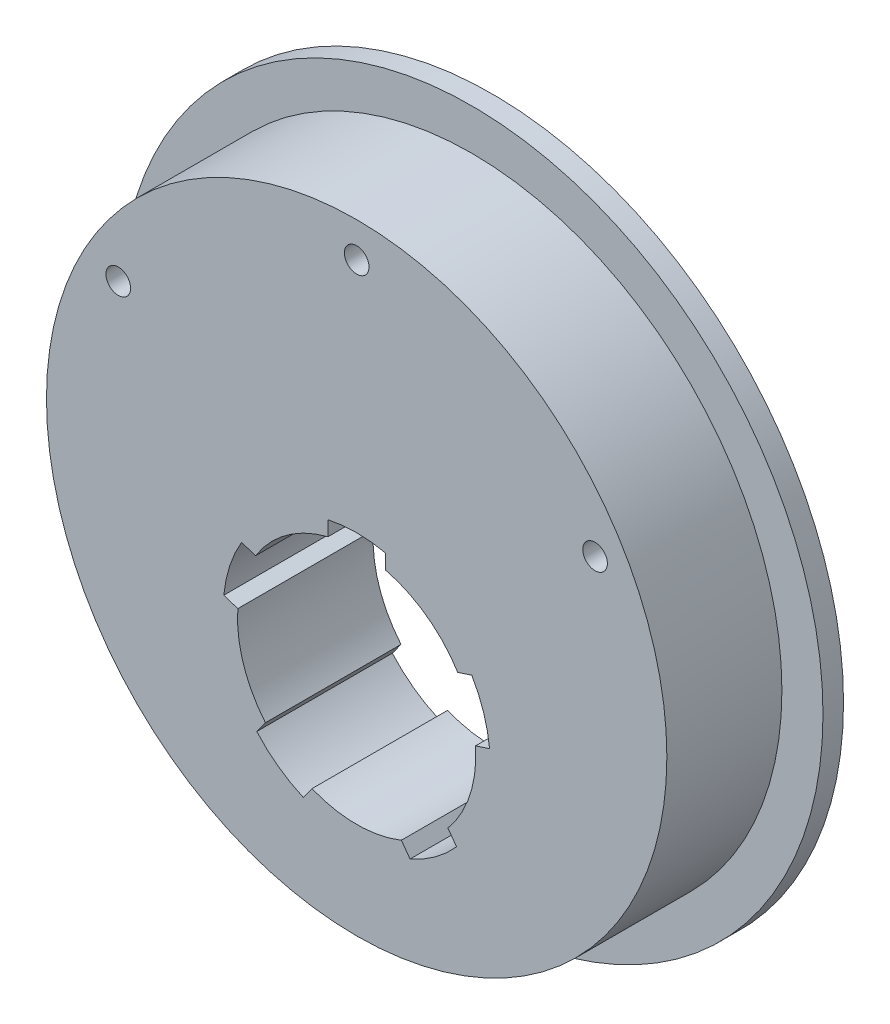
SolidWorks part; units mm, degrees
ref_plane "Front Plane" through (0, 0, 0) normal (0, 0, 1) x (1, 0, 0)
ref_plane "Top Plane" through (0, 0, 0) normal (0, 1, 0) x (1, 0, 0)
ref_plane "Right Plane" through (0, 0, 0) normal (1, 0, 0) x (0, 0, -1)
sketch "Sketch2" plane through (0, 0, 0) normal (0, 0, 1) x (1, 0, 0)
  circle A0 centre (0, 0) radius 85.5
  dimension "D1" = 171
extrude "Boss-Extrude1" add sketch "Sketch2" along normal blind 5
sketch "Sketch4" plane through (0, 0, 5) normal (0, 0, 1) x (1, 0, 0)
  circle A0 centre (0, 0) radius 75.5
  dimension "D1" = 151
extrude "Boss-Extrude2" add sketch "Sketch4" along normal blind 28
sketch "Sketch5" plane through (0, 0, 33) normal (0, 0, 1) x (1, 0, 0)
  circle A4 centre (0, -23) radius 29
  point P3 (0, 0)
  point P17 (-3.5, -55.5)
  dimension "D1" = 58
  dimension "D2" = 23
extrude "Cut-Extrude1" cut sketch "Sketch5" against normal through all
sketch "Sketch7" plane through (0, 0, 33) normal (0, 0, 1) x (1, 0, 0)
  line L0 (-7, 8.7372) -> (-7, 5.1425)
  line L1 (7, 8.7372) -> (7, 5.1425)
  arc A0 (7, 8.7372) -> (-7, 8.7372) centre (0, -23) ccw
  arc A1 (7, 5.1425) -> (-7, 5.1425) centre (0, -23) ccw
  dimension "D1" = 65
extrude "Cut-Extrude2" cut sketch "Sketch7" against normal through all both and the other way through all
pattern_circular "CirPattern1" count 5 over 360 about axis through (0, -23, 33) along (0, 0, 1) of "Cut-Extrude2"
sketch "Sketch10" plane through (0, 0, 33) normal (0, 0, 1) x (1, 0, 0)
  circle A0 centre (0, 0) radius 67 construction
  circle A1 centre (0, 67) radius 3
  point P5 (0, 0)
  dimension "D1" = 134
  dimension "D2" = 6
extrude "Cut-Extrude3" cut sketch "Sketch10" against normal blind 12
pattern_circular "CirPattern2" count 2 over 60 about axis through (0, 0, 5) along (0, 0, 1) of "Cut-Extrude3"
pattern_circular "CirPattern3" count 2 over 60 about axis through (0, 0, 33) along (0, 0, 1) of "CirPattern2" reverse direction yes
